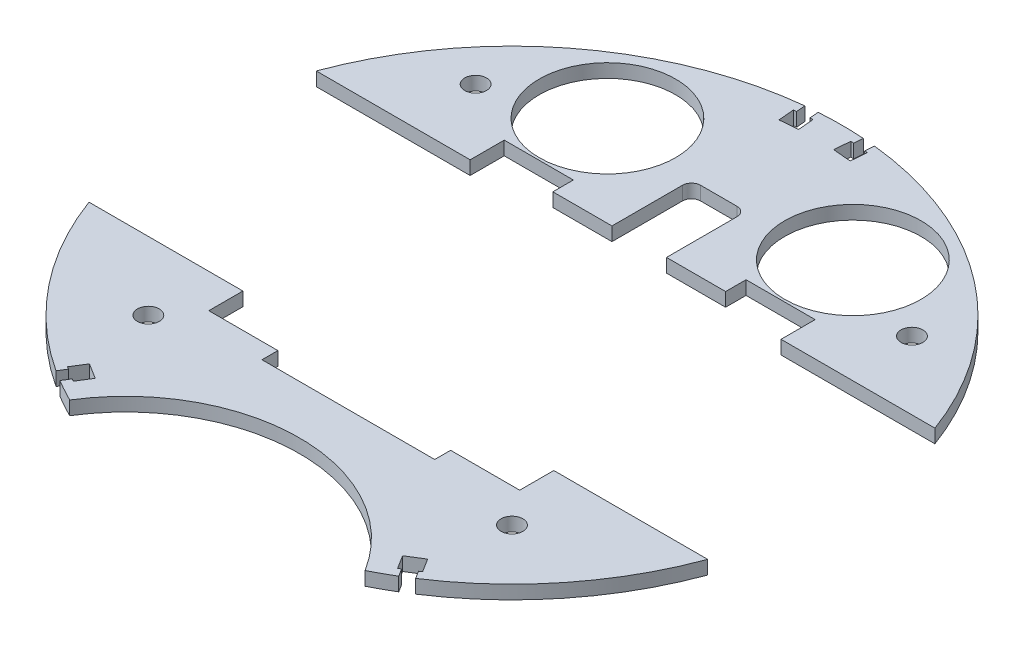
SolidWorks part; units mm, degrees
material "ABS"
ref_plane "Front Plane" through (0, 0, 0) normal (0, 0, 1) x (1, 0, 0)
ref_plane "Top Plane" through (0, 0, 0) normal (0, 1, 0) x (1, 0, 0)
ref_plane "Right Plane" through (0, 0, 0) normal (1, 0, 0) x (0, 0, -1)
sketch "Sketch1" plane through (0, 0, 0) normal (0, 1, 0) x (1, 0, 0)
  line L0 (0, -85) -> (-32.4891, -64.8129) construction
  line L1 (0, -85) -> (0, 0) construction
  arc A0 (32.4891, -64.8129) -> (-32.4891, -64.8129) centre (0, 0) ccw
  arc A1 (32.4891, -64.8129) -> (-32.4891, -64.8129) centre (0, -85) ccw
  dimension "D1" = 145
  dimension "D2" = 76.5
  dimension "D3" = 85
extrude "Boss-Extrude1" add sketch "Sketch1" along normal blind 3
sketch "solenoid placement" plane through (0, 3, 0) normal (0, 1, 0) x (1, 0, 0)
  line L4 (-19, -36) -> (19, -36)
  line L5 (-19, 28) -> (-19, -36)
  line L10 (19, 28) -> (-19, 28)
  line L11 (19, -36) -> (19, 28)
  line L12 (-19, -36) -> (19, -36)
  line L13 (-19, 28) -> (-19, -36)
  line L14 (19, 28) -> (-19, 28)
  line L15 (19, -36) -> (19, 28)
  dimension "D1" = 0
extrude "Cut-Extrude1" cut sketch "solenoid placement" against normal through all
sketch "Sketch7" plane through (0, 3, 0) normal (0, 1, 0) x (1, 0, 0)
  circle A3 centre (27, 48) radius 15
  circle A4 centre (27, 48) radius 15
  circle A5 centre (-27, 48) radius 15
  circle A6 centre (-27, 48) radius 15
  dimension "D1" = 0
  dimension "D2" = 0
extrude "Cut-Extrude6" cut sketch "Sketch7" against normal through all
sketch "Sketch8" plane through (0, 3, 0) normal (0, 1, 0) x (1, 0, 0)
  circle A1 centre (40, -40) radius 2.4
  circle A2 centre (40, -40) radius 2.4
  circle A3 centre (-40, -40) radius 2.4
  circle A4 centre (-40, -40) radius 2.4
  circle A5 centre (48, 40) radius 2.4
  circle A6 centre (48, 40) radius 2.4
  circle A7 centre (-48, 40) radius 2.4
  circle A8 centre (-48, 40) radius 2.4
  dimension "D1" = 0
  dimension "D2" = 0
  dimension "D3" = 0
  dimension "D4" = 0
extrude "Cut-Extrude7" cut sketch "Sketch8" against normal through all
sketch "Sketch3" plane through (0, 3, 0) normal (0, 1, 0) x (1, 0, 0)
  line L1 (-34.2, -32.5) -> (-22.2, -32.5)
  line L2 (-34.2, 25) -> (-68.0533, 25)
  line L3 (-34.2, 32.5) -> (-22.2, 32.5)
  line L4 (-22.2, -32.5) -> (-22.2, 32.5) construction
  line L8 (0, 0) -> (0, 72.5) construction
  line L17 (-34.2, -32.5) -> (-34.2, -25)
  line L18 (-34.2, -25) -> (-68.0533, -25)
  line L19 (-34.2, 25) -> (-34.2, 32.5)
  line L21 (-22.2, 32.5) -> (-19, 32.5)
  line L22 (-22.2, 32.5) -> (-22.2, -32.5) construction
  line L23 (-22.2, -32.5) -> (-19, -32.5)
  line L24 (-19, 32.5) -> (-19, -32.5)
  line L25 (22.2, 32.5) -> (22.2, -32.5) construction
  line L26 (22.2, -32.5) -> (22.2, 32.5) construction
  line L27 (19, 32.5) -> (19, -32.5)
  line L28 (22.2, -32.5) -> (19, -32.5)
  line L29 (22.2, 32.5) -> (19, 32.5)
  line L30 (34.2, 25) -> (34.2, 32.5)
  line L31 (34.2, -25) -> (68.0533, -25)
  line L32 (34.2, -32.5) -> (34.2, -25)
  line L33 (34.2, 32.5) -> (22.2, 32.5)
  line L34 (34.2, 25) -> (68.0533, 25)
  line L35 (34.2, -32.5) -> (22.2, -32.5)
  line L36 (-19, 28) -> (-19, -36) construction
  arc A0 (32.4891, -64.8129) -> (-32.4891, -64.8129) centre (0, 0) ccw construction
  arc A2 (68.0533, 25) -> (68.0533, -25) centre (0, 0) cw
  arc A3 (-68.0533, 25) -> (-68.0533, -25) centre (0, 0) ccw
  point P31 (-34.2, -32.5)
  dimension "D1" = 50
extrude "Cut-Extrude3" cut sketch "Sketch3" against normal through all
sketch "Sketch9" plane through (0, 3, 0) normal (0, 1, 0) x (1, 0, 0)
  line L0 (6, 43.5) -> (6, 28)
  line L1 (-6, 43.5) -> (-6, 28)
  line L2 (19, 28) -> (-19, 28) construction
  line L8 (-6, 28) -> (6, 28)
  line L10 (4, 45.5) -> (-4, 45.5)
  arc A0 (-6, 43.5) -> (-4, 45.5) centre (-4, 43.5) cw
  arc A1 (6, 43.5) -> (4, 45.5) centre (4, 43.5) ccw
  point P5 (0, 28)
  point P6 (0, 28)
  point P16 (-6, 45.5)
  point P19 (6, 45.5)
  dimension "D3" = 2
  dimension "D2" = 12
  dimension "D1" = 17.5
extrude "Cut-Extrude8" cut sketch "Sketch9" against normal through all
sketch "Sketch10" plane through (0, 3, 0) normal (0, 1, 0) x (1, 0, 0)
  line L0 (0, 0) -> (0, 72.5) construction
  line L1 (0, 0) -> (6.3188, 72.2241) construction
  line L2 (3.847, 66.9194) -> (7.8318, 66.5707)
  line L3 (3.847, 66.9194) -> (4.1521, 70.406)
  line L4 (7.8318, 66.5707) -> (8.1369, 70.0574)
  line L5 (4.1521, 70.406) -> (4.7996, 70.3494)
  line L6 (4.7996, 70.3494) -> (4.9739, 72.3418)
  line L7 (4.9739, 72.3418) -> (7.6637, 72.1065)
  line L8 (7.6637, 72.1065) -> (7.4893, 70.1141)
  line L9 (7.4893, 70.1141) -> (8.1369, 70.0574)
  line L10 (-7.4893, 70.1141) -> (-8.1369, 70.0574)
  line L11 (-7.6637, 72.1065) -> (-7.4893, 70.1141)
  line L12 (-4.9739, 72.3418) -> (-7.6637, 72.1065)
  line L13 (-4.7996, 70.3494) -> (-4.9739, 72.3418)
  line L14 (-4.1521, 70.406) -> (-4.7996, 70.3494)
  line L15 (-7.8318, 66.5707) -> (-8.1369, 70.0574)
  line L16 (-3.847, 66.9194) -> (-4.1521, 70.406)
  line L17 (-3.847, 66.9194) -> (-7.8318, 66.5707)
  line L18 (37.2007, -55.7594) -> (33.8085, -57.8791)
  line L19 (37.2007, -55.7594) -> (39.0554, -58.7276)
  line L20 (33.8085, -57.8791) -> (35.6632, -60.8472)
  line L21 (39.0554, -58.7276) -> (38.5042, -59.072)
  line L22 (38.5042, -59.072) -> (39.564, -60.7681)
  line L23 (39.564, -60.7681) -> (37.2743, -62.1989)
  line L24 (37.2743, -62.1989) -> (36.2144, -60.5028)
  line L25 (36.2144, -60.5028) -> (35.6632, -60.8472)
  line L26 (0, 0) -> (38.4191, -61.4835) construction
  line L27 (0, 0) -> (0, -85) construction
  line L28 (-33.8085, -57.8791) -> (-37.2007, -55.7594)
  line L29 (-33.8085, -57.8791) -> (-35.6632, -60.8472)
  line L30 (-37.2007, -55.7594) -> (-39.0554, -58.7276)
  line L31 (-35.6632, -60.8472) -> (-36.2144, -60.5028)
  line L32 (-36.2144, -60.5028) -> (-37.2743, -62.1989)
  line L33 (-37.2743, -62.1989) -> (-39.564, -60.7681)
  line L34 (-39.564, -60.7681) -> (-38.5042, -59.072)
  line L35 (-38.5042, -59.072) -> (-39.0554, -58.7276)
  line L36 (0, 0) -> (-38.4191, -61.4835) construction
  arc A1 (68.0533, 25) -> (-68.0533, 25) centre (0, 0) ccw construction
  point P1 (5.8394, 66.745)
  point P15 (6.3188, 72.2241)
  point P26 (0, 0)
  point P36 (0, 0)
  point P49 (0, 0)
  dimension "D1" = 3.5
  dimension "D2" = 4
  dimension "D3" = 5
  dimension "D4" = 2.7
  dimension "D5" = 2
  dimension "D7" = 32
  dimension "D9" = 32
  dimension "D6" = 2
  dimension "D8" = 2
extrude "Cut-Extrude9" cut sketch "Sketch10" against normal through all
equation "\"smallPulleyTeeth\"= 30"
equation "\"largePulleyTeeth\"= 30"
equation "\"eighthThick\"= 3.0mm"
equation "\"sixteenthThick\" = 1.7mm"
equation "\"quarterThick\"=6.0mm"
equation "\"OD\" = 145mm"
equation "\"puckAngle\" = 60.5deg"
equation "\"D1@Sketch1\"=\"OD\""
equation "\"puckDiam\" = 76.5mm"
equation "\"D2@Sketch1\"=\"puckDiam\""
equation "\"D1@Boss-Extrude1\"=\"eighthThick\""
equation "\"axlePress\" = 5.9mm"
equation "\"press\" = 0.2mm"
equation "\"wheelClear\" = 0.3mm"
equation "\"10-32clear\" = 4.8mm"
equation "\"6-32clear\" = 3.3mm"
equation "\"8-32clear\" = 4.0mm"
equation "\"4-40clear\" = 3.0mm"
equation "\"wheelHeight\" = 22mm"
equation "\"wheelWell\" = 65mm"
equation "\"puckDist\" = 85mm"
equation "\"D3@Sketch1\"=\"puckDist\""
equation "\"scoopFillet\" = 5mm"
equation "\"10-32tap\" = 4.45mm"
equation "\"ledSmall\" = 3.1mm"
equation "\"ledLarge\" = 4.2mm"
equation "\"ledLength\" = 4.2mm"
equation "\"4-40close\" = 2.7mm"
equation "\"4-40nutThick\" = 2.2mm"
equation "\"4-40nutWidth\" = 6.2mm"
equation "\"4-40insertHeight\" = 3.5mm"
equation "\"4-40insert\" = 4mm"
equation "\"D1@Sketch10\"=\"4-40insertHeight\""
equation "\"D2@Sketch10\"=\"4-40insert\""
equation "\"D4@Sketch10\"=\"4-40close\""
